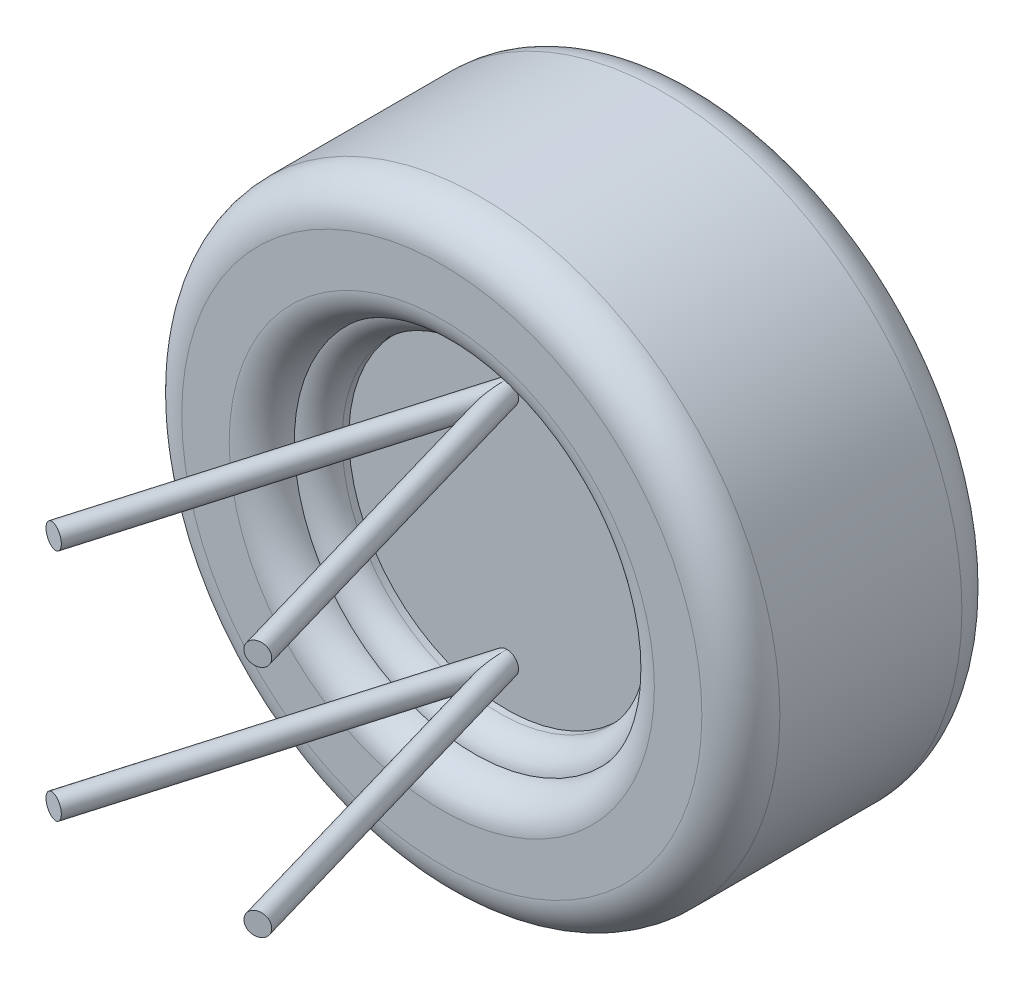
SolidWorks part; units mm, degrees
material "HYPALON"
ref_plane "정면" through (0, 0, 0) normal (0, 0, 1) x (1, 0, 0)
ref_plane "윗면" through (0, 0, 0) normal (0, 1, 0) x (1, 0, 0)
ref_plane "우측면" through (0, 0, 0) normal (1, 0, 0) x (0, 0, -1)
sketch "스케치1" plane through (0, 0, 0) normal (0, 0, 1) x (1, 0, 0)
  circle A0 centre (0, 0) radius 230
  dimension "D1" = 460
extrude "보스-돌출1" add sketch "스케치1" along normal blind 200 contours A0
sketch "스케치4" plane through (0, 0, 200) normal (0, 0, 1) x (1, 0, 0)
  circle A0 centre (0, 0) radius 138.5
  dimension "D1" = 277
extrude "컷-돌출1" cut sketch "스케치4" against normal blind 25 contours A0
sketch "스케치5" plane through (0, 0, 175) normal (0, 0, 1) x (1, 0, 0)
  circle A0 centre (0, 0) radius 121.5
  dimension "D1" = 243
extrude "컷-돌출2" cut sketch "스케치5" against normal blind 25
sketch "스케치6" plane through (0, 0, 0) normal (0, 0, -1) x (-1, 0, 0)
  circle A0 centre (0, 0) radius 131.5
  dimension "D1" = 263
extrude "컷-돌출3" cut sketch "스케치6" against normal blind 25
fillet "필렛1" radius 25 2 edges at (138.5, 0, 200) (-131.5, 0, 0)
fillet "필렛2" radius 20 1 edges at (121.5, 0, 175)
fillet "필렛3" radius 30 2 edges at (230, 0, 0) (230, 0, 200)
sketch "스케치7" plane through (0, 0, 150) normal (0, 0, 1) x (1, 0, 0)
  point P0 (0, 90)
  point P1 (0, -90)
  dimension "D1" = 180
  dimension "D2" = 90
ref_plane "평면1" through (0, 0, 420) normal (0, 0, 1) x (1, 0, 0)
sketch "스케치8" plane through (0, 0, 420) normal (0, 0, 1) x (1, 0, 0)
  point P0 (-78.5, 90)
  point P1 (78.5, 90)
  point P2 (-78.5, -90)
  point P5 (78.5, -90)
  dimension "D1" = 157
  dimension "D2" = 78.5
sketch3d "3D스케치2"
  line L0 (0, 90, 150) -> (78.5, 90, 420)
  line L1 (0, 90, 150) -> (-78.5, 90, 420)
  line L2 (0, -90, 150) -> (78.5, -90, 420)
  line L3 (0, -90, 150) -> (-78.5, -90, 420)
other "종류 17.3_CIRCLE(1)"
ref_plane "평면2" through (0, 90, 150) normal (-0.2792, 0, 0.9602) x (0.9602, 0, 0.2792)
sketch "스케치11" plane through (0, 90, 150) normal (-0.2792, 0, 0.9602) x (0.9602, 0, 0.2792)
  circle A0 centre (0, 0) radius 8.65
  point P3 (0, 0)
  dimension "D1" = 17.3
other "종류 17.3_CIRCLE(2)"
ref_plane "평면3" through (0, -90, 150) normal (0.2792, 0, 0.9602) x (0.9602, 0, -0.2792)
sketch "스케치12" plane through (0, -90, 150) normal (0.2792, 0, 0.9602) x (0.9602, 0, -0.2792)
  circle A0 centre (0, 0) radius 8.65
  point P3 (0, 0)
  dimension "D1" = 17.3
ref_plane "평면5" through (0, 0, 100) normal (0, 0, 1) x (1, 0, 0)
sketch "스케치16" plane through (0, 0, 100) normal (0, 0, 1) x (1, 0, 0)
  line L0 (-50, -234.4994) -> (50, -234.4994)
  line L1 (-50, -234.4994) -> (-50, -224.4994)
  line L2 (50, -234.4994) -> (50, -224.4994)
  circle A0 centre (0, 0) radius 230 construction
  arc A1 (-50, -224.4994) -> (50, -224.4994) centre (0, 0) ccw
  dimension "D1" = 100
  dimension "D2" = 50
  dimension "D3" = 10
extrude "보스-돌출2" add sketch "스케치16" along normal mid plane 100
fillet "필렛5" radius 3.5 4 edges at (-50, -224.4994, 100) (0, -230, 50) (50, -224.4994, 100) (0, -230, 150)
